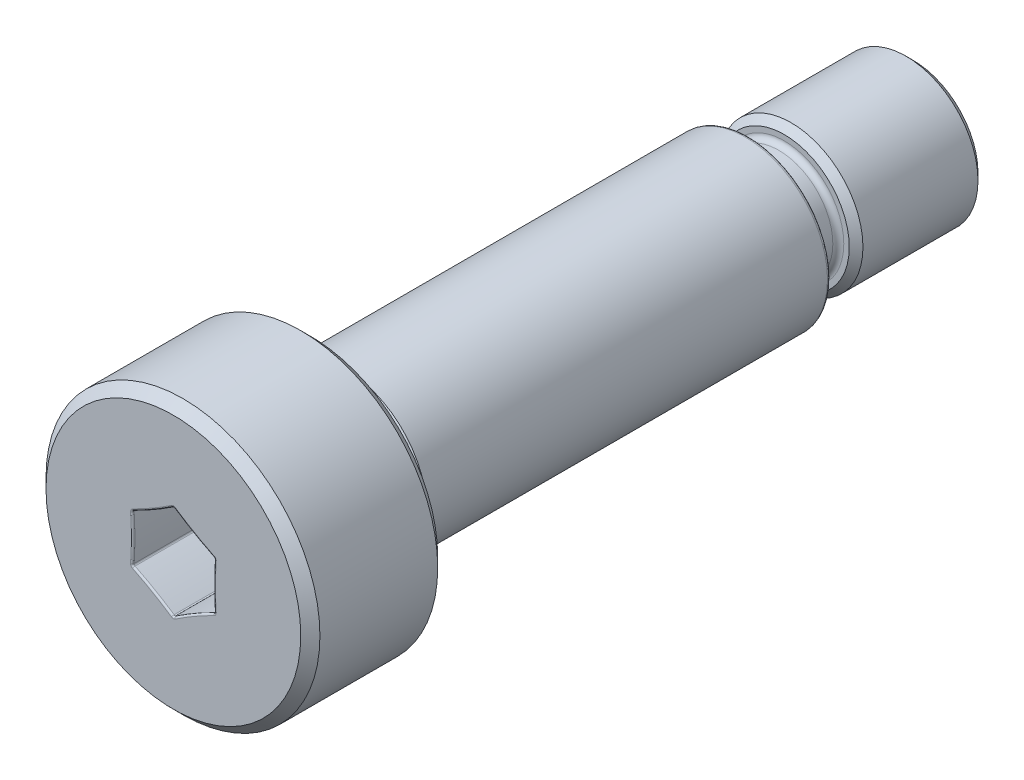
SolidWorks part; units mm, degrees
material "Alloy Steel (SS)"
ref_plane "Front Plane" through (0, 0, 0) normal (0, 0, 1) x (1, 0, 0)
ref_plane "Top Plane" through (0, 0, 0) normal (0, 1, 0) x (1, 0, 0)
ref_plane "Right Plane" through (0, 0, 0) normal (1, 0, 0) x (0, 0, -1)
sketch "Sketch1" plane through (0, 0, 0) normal (0, 0, 1) x (1, 0, 0)
  line L1 (1.1906, 0.6874) -> (0, 1.3748)
  line L2 (0, 1.3748) -> (-1.1906, 0.6874)
  line L3 (-1.1906, 0.6874) -> (-1.1906, -0.6874)
  line L4 (-1.1906, -0.6874) -> (0, -1.3748)
  line L5 (0, -1.3748) -> (1.1906, -0.6874)
  line L6 (1.1906, -0.6874) -> (1.1906, 0.6874)
  circle A0 centre (0, 0) radius 3.9688
  circle A1 centre (0, 0) radius 2.3813
  circle A2 centre (0, 0) radius 2.0828
  circle A3 centre (0, 0) radius 1.1906 construction
  dimension "Head Diameter" = 7.9375
  dimension "Shoulder Diameter" = 4.7625
  dimension "Screw Size Decimal Equivalent" = 4.1656
  dimension "Drive Size" = 2.3813
sketch "Sketch2" plane through (0, 0, 0) normal (1, 0, 0) x (0, 0, -1)
  line L0 (17.4625, 2.0828) -> (0, 2.0828) construction
  line L1 (0, 3.9688) -> (-3.9688, 3.9687) construction
  line L2 (12.7, 2.3813) -> (0, 2.3813) construction
  line L3 (0, -3.9688) -> (-3.9688, -3.9688) construction
  line L6 (0, -2.0828) -> (17.4625, -2.0828) construction
  line L9 (17.4129, 2.1687) -> (18.2066, 2.1687) construction
  line L10 (18.2066, 2.1687) -> (17.8098, 1.4813) construction
  line L11 (17.8098, 1.4813) -> (17.4129, 2.1687) construction
  line L12 (17.4625, 2.0828) -> (18.157, 2.0828) construction
  line L13 (17.7602, 1.5672) -> (17.8594, 1.5672) construction
  line L14 (17.8098, 1.5672) -> (17.8098, 1.4813) construction
  line L15 (17.8098, 2.1687) -> (17.8098, 2.0828) construction
  line L16 (17.4377, 2.1258) -> (18.1818, 2.1258) construction
  line L17 (-3.9688, 0) -> (17.4625, 0) construction
  line L18 (12.7, 2.3813) -> (12.7, -2.0828) construction
  point P23 (17.8098, 2.1258)
  point P24 (16.6687, 2.0828)
  dimension "Head Height" = 3.9688
  dimension "Shoulder Length" = 12.7
  dimension "Thread Length" = 4.7625
  dimension "Thread Pitch" = 0.7937
  dimension "D2" = 0.0992
  dimension "Thread Note" = 0.7937
sketch "Sketch3" plane through (0, 0, 0) normal (1, 0, 0) x (0, 0, -1)
  line L0 (-3.9688, 3.9687) -> (0, 3.9688)
  line L1 (0, 3.9688) -> (0, 2.3813)
  line L2 (0, 2.3813) -> (12.7, 2.3813)
  line L3 (12.7, 2.3813) -> (12.7, 2.0828)
  line L4 (17.4625, 2.0828) -> (0, 2.0828) construction
  line L5 (12.7, 2.0828) -> (17.4625, 2.0828)
  line L6 (17.4625, 2.0828) -> (17.4625, 0)
  line L7 (17.4625, 0) -> (-3.9688, 0)
  line L8 (-3.9688, 0) -> (-3.9688, 3.9687)
  line L9 (-3.9688, 0) -> (17.4625, 0) construction
revolve "Revolve1" add sketch "Sketch3" angle 360 about L17
sketch "Sketch4" plane through (0, 0, 0) normal (1, 0, 0) x (0, 0, -1)
  line L0 (-3.9688, 0) -> (17.4625, 0) construction
  line L1 (0, 2.3813) -> (0.9922, 2.3813)
  line L2 (0, 2.3813) -> (0, 2.0241)
  line L3 (0, 2.0241) -> (0.9922, 2.0241)
  line L4 (0.9922, 2.3813) -> (0.9922, 2.0241)
  line L5 (17.4625, 2.0828) -> (0, 2.0828) construction
  line L6 (12.7, 2.0828) -> (13.7319, 2.0828)
  line L7 (12.7, 2.0828) -> (12.7, 1.5672)
  line L8 (12.7, 1.5672) -> (13.7319, 1.5672)
  line L9 (13.7319, 2.0828) -> (13.7319, 1.5672)
  line L10 (17.7602, 1.5672) -> (17.8594, 1.5672) construction
  line L12 (6.35, 2.3813) -> (6.35, 0) construction
  line L13 (12.7, 2.3813) -> (0, 2.3813) construction
  point P22 (1.528, 2.0241)
  point P23 (11.172, 2.0241)
  dimension "D1" = 0.9922
  dimension "D2" = 4.0481
  dimension "D3" = 1.0319
  dimension "D4" = 9.6441
revolve "Cut-Revolve1" cut sketch "Sketch4" angle 360 about L17
chamfer "Chamfer1" distance 0.3572 angle 45 1 edges at (2.0241, 0, -0.9922)
fillet "Fillet1" radius 0.1786 1 edges at (2.0241, 0, 0)
fillet "Fillet2" radius 0.1588 2 edges at (1.5672, 0, -12.7) (1.5672, 0, -13.7319)
chamfer "Chamfer2" distance 0.1984 angle 45 2 edges at (2.0828, 0, -13.7319) (2.0828, 0, -17.4625)
fillet "Fillet3" radius 0.0953 1 edges at (2.3813, 0, -12.7)
chamfer "Chamfer3" distance 0.2778 angle 45 2 edges at (3.9688, 0, 0) (3.9687, 0, 3.9688)
sketch "Sketch5" plane through (0, 0, 3.9688) normal (0, 0, 1) x (1, 0, 0)
  arc A0 (1.1906, 0.6874) -> (0, 1.3748) centre (5.5503, 9.6134) cw
  circle A2 centre (0, 0) radius 1.1668 construction
  arc A3 (1.1906, -0.6874) -> (1.1906, 0.6874) centre (11.1006, 0) cw
  arc A4 (0, -1.3748) -> (1.1906, -0.6874) centre (5.5503, -9.6134) cw
  arc A5 (-1.1906, -0.6874) -> (0, -1.3748) centre (-5.5503, -9.6134) cw
  arc A6 (-1.1906, 0.6874) -> (-1.1906, -0.6874) centre (-11.1006, 0) cw
  arc A7 (0, 1.3748) -> (-1.1906, 0.6874) centre (-5.5503, 9.6134) cw
  point P25 (0, 0)
  dimension "D1" = 2.3336
  dimension "D2" = 6
extrude "Cut-Extrude1" cut sketch "Sketch5" against normal blind 2.0828
fillet "Fillet4" radius 0.0508 18 edges at (1.1668, 0, 3.9688) (1.1906, -0.6874, 2.9274) (0.5834, -1.0105, 3.9688) (0, -1.3748, 2.9274) (-0.5834, -1.0105, 3.9688) (-1.1906, -0.6874, 2.9274) (-1.1668, 0, 3.9688) (-1.1906, 0.6874, 2.9274) (-0.5834, 1.0105, 3.9688) (1.1906, 0.6874, 2.9274) (0, 1.3748, 2.9274) (0.5834, 1.0105, 3.9688) (0.5834, -1.0105, 1.886) (-0.5834, -1.0105, 1.886) (-1.1668, 0, 1.886) (-0.5834, 1.0105, 1.886) (0.5834, 1.0105, 1.886) (1.1668, 0, 1.886)
sketch "Sketch6" [suppressed] plane through (0, 0, -17.4625) normal (0, 0, -1) x (-1, 0, 0)
  circle A0 centre (0, 0) radius 2.0828
  circle A1 centre (0, 0) radius 2.0828 construction
sketch "Sketch7" [suppressed] plane through (0, 0, 0) normal (1, 0, 0) x (0, 0, -1)
  line L0 (17.4377, 2.1258) -> (18.1818, 2.1258)
  line L1 (18.1818, 2.1258) -> (17.8594, 1.5672)
  line L2 (17.8594, 1.5672) -> (17.7602, 1.5672)
  line L3 (17.7602, 1.5672) -> (17.4377, 2.1258)
other "DeleteFace1" [suppressed]
curve "Helix/Spiral1" [suppressed] pitch 0.7937 height 4.3497 turns 5.48
sweep "Cut-Sweep1" [suppressed] cut profiles "Sketch7" path "Helix/Spiral1"
equation "\"D2@Sketch2\" = \"Thread Pitch@Sketch2\" / 8"
equation "\"D1@Sketch4\" = \"Head Height@Sketch2\" * .25"
equation "\"D3@Sketch4\" = \"Thread Pitch@Sketch2\" * 1.3"
equation "\"D2@Sketch4\" = \"Shoulder Diameter@Sketch1\" * .85"
equation "\"D1@Chamfer1\" =  ( \"Shoulder Diameter@Sketch1\" - \"D2@Sketch4\" )  * .5"
equation "\"D1@Fillet1\"=\"d1@chaMFER1\"*.5"
equation "\"D1@Fillet2\"=\"Thread Pitch@Sketch2\"*.2"
equation "\"D1@Chamfer2\"=\"Thread Pitch@Sketch2\"*.25"
equation "\"D1@Fillet3\"=\"Shoulder Diameter@Sketch1\"*.02"
equation "\"D1@Chamfer3\" = \"Head Height@Sketch2\" * .07"
equation "\"D1@Sketch5\"=\"Drive Size@Sketch1\"*.98"
equation "\"D1@Cut-Extrude1\"=\"Screw Size Decimal Equivalent@Sketch1\"*.5"
equation "\"D4@Helix/Spiral1\"=\"thread pitch@sketch2\""
equation "\"D3@Helix/Spiral1\"=\"Thread Length@Sketch2\" - \"D3@Sketch4\" * .4"
equation "\"D4@Sketch4\"=(\"Shoulder Length@Sketch2\"-(2*\"D1@Sketch4\"))*.9"
equation "\"Thread Note@Sketch2\"=\"Thread Pitch@Sketch2\" * 1"
